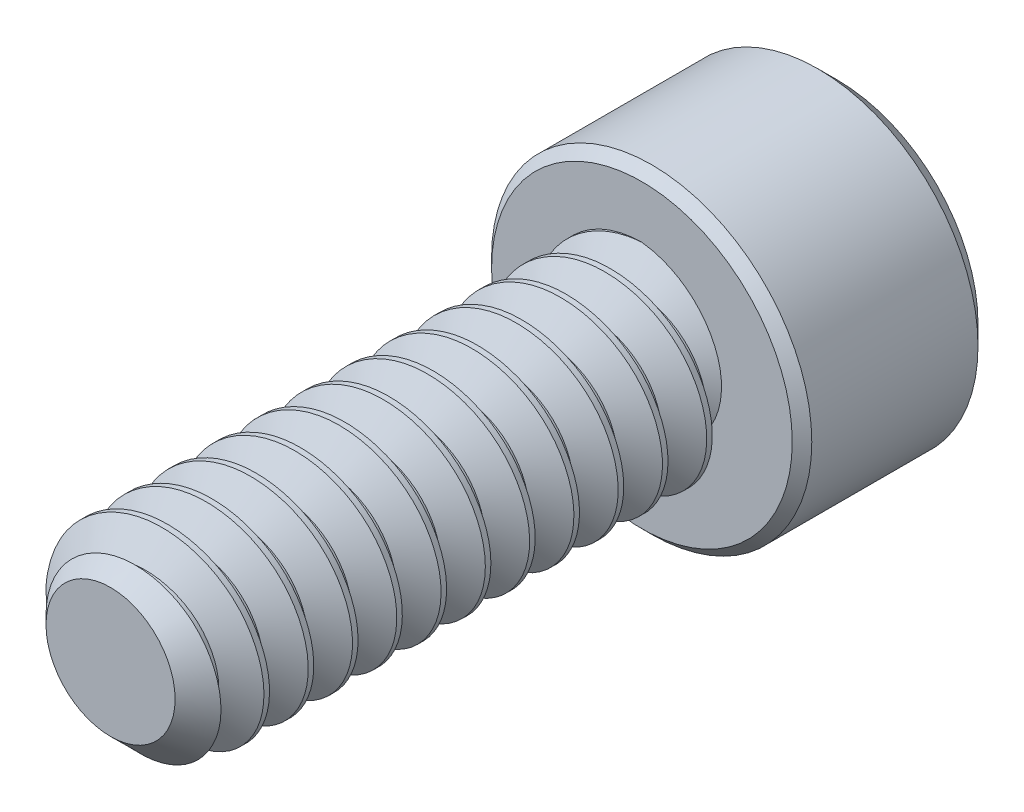
SolidWorks part; units mm, degrees
material "Plain Carbon Steel"
ref_plane "Front Plane" through (0, 0, 0) normal (0, 0, 1) x (1, 0, 0)
ref_plane "Top Plane" through (0, 0, 0) normal (0, 1, 0) x (1, 0, 0)
ref_plane "Right Plane" through (0, 0, 0) normal (1, 0, 0) x (0, 0, -1)
sketch "Sketch1" plane through (0, 0, 0) normal (0, 0, 1) x (1, 0, 0)
  line L0 (0, 1.7526) -> (0, -1.7526) construction
  circle A0 centre (0, 0) radius 1.7526
  dimension "OD" = 3.5052
extrude "Extrude1" add sketch "Sketch1" against normal blind 9.525
sketch "Sketch2" plane through (0, 0, 0) normal (0, 0, 1) x (1, 0, 0)
  circle A0 centre (0, 0) radius 1.7526 construction
  circle A1 centre (0, 0) radius 1.7526
curve "Helix/Spiral1" pitch 0.7937 height 10.3188 turns 13 parameters "pitch"=0.7937
chamfer "Chamfer3" distance 0.5953 angle 45 1 edges at (1.7526, 0, 0)
sketch "Sketch3" plane through (0, 0, 0) normal (1, 0, 0) x (0, 0, -1)
  line L0 (-0.6945, 1.7526) -> (-0.3969, 1.237)
  line L1 (-0.3969, 1.237) -> (-0.2977, 1.237)
  line L2 (-0.2977, 1.237) -> (0, 1.7526)
  line L3 (-0.6945, 1.7526) -> (0, 1.7526)
  line L4 (-0.3473, 1.7526) -> (-0.3473, 1.237) construction
  line L5 (-0.5457, 1.4948) -> (-0.1488, 1.4948) construction
  line L6 (0, 1.7526) -> (0, -1.7526) construction
  dimension "D1" = 0.0992
  dimension "D2" = 0.3969
  dimension "D3" = 60
sweep "Cut-Sweep1" cut profiles "Sketch3" path "Helix/Spiral1"
sketch "Sketch6" plane through (0, 0, -9.525) normal (0, 0, -1) x (-1, 0, 0)
  circle A0 centre (0, 0) radius 2.8702
  dimension "head dia" = 5.7404
extrude "Extrude2" add sketch "Sketch6" along normal blind 3.5052
sketch "Sketch7" plane through (0, 0, -13.0302) normal (0, 0, -1) x (-1, 0, 0)
  line L1 (0, 1.604) -> (-1.3891, 0.802)
  line L2 (-1.3891, 0.802) -> (-1.3891, -0.802)
  line L3 (-1.3891, -0.802) -> (0, -1.604)
  line L4 (0, -1.604) -> (1.3891, -0.802)
  line L5 (1.3891, -0.802) -> (1.3891, 0.802)
  line L6 (1.3891, 0.802) -> (0, 1.604)
  circle A0 centre (0, 0) radius 1.3891 construction
  dimension "hex dia" = 2.7781
extrude "Cut-Extrude1" cut sketch "Sketch7" against normal blind 2.0836
sketch "Sketch8" plane through (0, 0, -13.0302) normal (0, 0, -1) x (-1, 0, 0)
  circle A0 centre (0, 0) radius 1.604
extrude "Cut-Extrude2" cut sketch "Sketch8" against normal blind 0.3505 draft 45
chamfer "Chamfer1" distance 0.3505 angle 45 1 edges at (-2.8702, 0, -13.0302)
chamfer "Chamfer2" distance 0.1753 angle 45 1 edges at (-2.8702, 0, -9.525)
sketch "Sketch9" plane through (0, 0, 0) normal (1, 0, 0) x (0, 0, -1)
  line L0 (0, 1.7526) -> (0, -1.7526) construction
  line L1 (4.3656, 1.7526) -> (4.3656, -1.7526) construction
  line L2 (9.525, 2.8702) -> (9.525, -2.8702) construction
  line L3 (13.0302, 2.8702) -> (13.0302, -2.8702) construction
  line L4 (13.0302, 0) -> (0, 0) construction
  dimension "D1" = 4.3656
  dimension "D2" = 3.5052
  dimension "D3" = 5.7404
  dimension "D4" = 9.525
equation "\"D3@Helix/Spiral1\" = \"screw length@Extrude1\"+\"pitch@Helix/Spiral1\""
equation "\"D1@Sketch3\" = \"pitch@Helix/Spiral1\"*.125"
equation "\"D2@Sketch3\" = \"pitch@Helix/Spiral1\"*.5"
equation "\"D1@Cut-Extrude1\" = \"hex dia@Sketch7\"*.75"
equation "\"D1@Chamfer1\" = \"head depth@Extrude2\"/10"
equation "\"D1@Sketch9\" = \"pitch@Helix/Spiral1\"*5.5"
equation "\"D1@Chamfer2\" = \"D1@Chamfer1\"/2"
equation "\"D1@Cut-Extrude2\" = \"D1@Chamfer2\"*2"
equation "\"D1@Chamfer3\" = \"pitch@Helix/Spiral1\"*.750"
equation "\"D2@Sketch9\" = \"head depth@Extrude2\""
equation "\"D3@Sketch9\" = \"head dia@Sketch6\""
equation "\"D4@Sketch9\" = \"screw length@Extrude1\""
